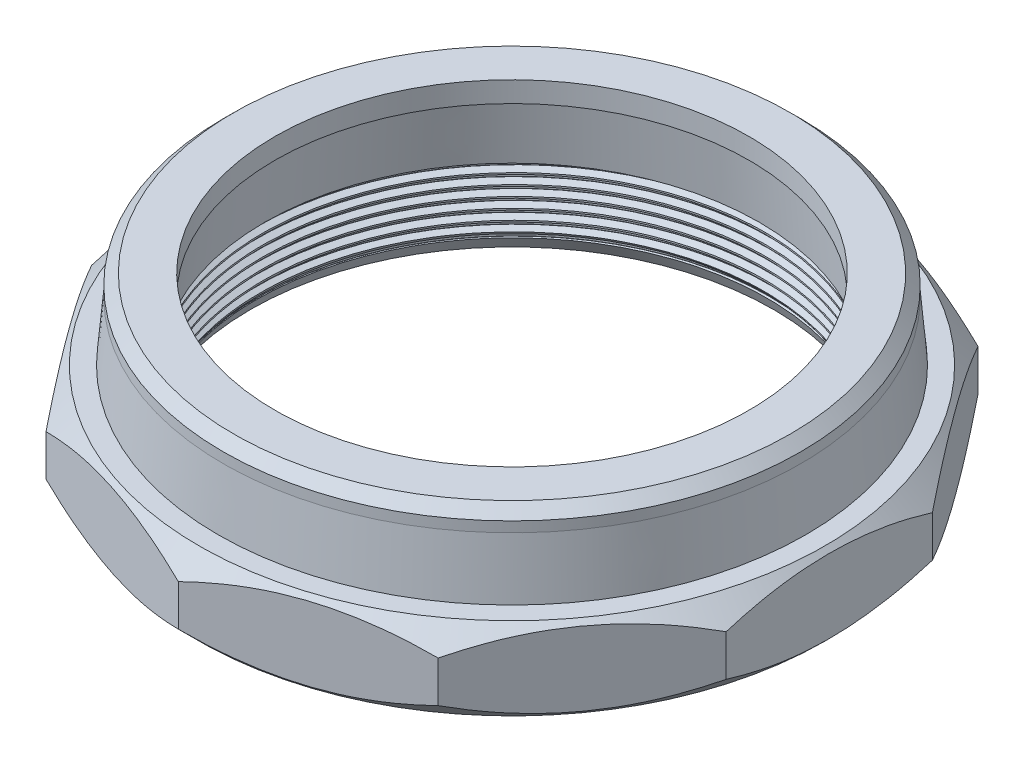
SolidWorks part; units mm, degrees
material "ABS"
ref_plane "Спереди" through (0, 0, 0) normal (0, 0, 1) x (1, 0, 0)
ref_plane "Сверху" through (0, 0, 0) normal (0, 1, 0) x (1, 0, 0)
ref_plane "Справа" through (0, 0, 0) normal (1, 0, 0) x (0, 0, -1)
sketch "Эскиз1" plane through (0, 0, 0) normal (0, 0, 1) x (1, 0, 0)
  line L0 (0, 9.0507) -> (0, -9.1503) construction
  line L1 (24.36, -8) -> (24.36, 0)
  line L3 (24.36, -8) -> (29.3544, -8)
  line L5 (28.5, 0) -> (28, 5.715)
  line L7 (23.5, 5.715) -> (23, 5.715)
  line L8 (23, 5.715) -> (23, 7.715)
  line L9 (23, 7.715) -> (28, 7.715)
  line L10 (28, 7.715) -> (28, 5.715)
  line L11 (28.5, 0) -> (30.36, 0)
  line L12 (32.36, -2) -> (32.36, -6)
  line L13 (30.36, -8) -> (29.3544, -8)
  line L14 (30.36, 0) -> (32.36, -2)
  line L15 (32.36, -6) -> (30.36, -8)
  line L18 (24, 0) -> (23.5, 5.715)
  line L19 (24, 0) -> (24.36, 0)
  dimension "D2" = 2
  dimension "D3" = 24.36
  dimension "D4" = 2
  dimension "D5" = 45
  dimension "D6" = 45
  dimension "D7" = 24
  dimension "D8" = 5
  dimension "D9" = 23
  dimension "D10" = 6
  dimension "D11" = 2
  dimension "D12" = 5
  dimension "D13" = 8
  dimension "D14" = 8
  dimension "D15" = 0.5
revolve "Повернуть1" add sketch "Эскиз1" angle 360 about L0
sketch "Эскиз2" plane through (0, 0, 0) normal (0, 1, 0) x (1, 0, 0)
  line L0 (0, 32.36) -> (0, -32.36) construction
  line L10 (0, 32.36) -> (-19.0207, 26.1798)
  line L11 (-19.0207, 26.1798) -> (-30.7762, 9.9998)
  line L12 (-30.7762, 9.9998) -> (-30.7762, -9.9998)
  line L13 (-30.7762, -9.9998) -> (-19.0207, -26.1798)
  line L14 (-19.0207, -26.1798) -> (0, -32.36)
  line L15 (0, -32.36) -> (19.0207, -26.1798)
  line L16 (19.0207, -26.1798) -> (30.7762, -9.9998)
  line L17 (30.7762, -9.9998) -> (30.7762, 9.9998)
  line L18 (30.7762, 9.9998) -> (19.0207, 26.1798)
  line L19 (19.0207, 26.1798) -> (0, 32.36)
  circle A0 centre (0, 0) radius 32.36 construction
  circle A1 centre (0, 0) radius 30.7762 construction
extrude "Вырез-Вытянуть3" cut sketch "Эскиз2" against normal blind 10 flip side to cut
chamfer "Фаска1" distance 2 distance2 1 1 edges at (-24.36, -8, 0) first distance on face at (-24.36, -8, 0)
chamfer "Фаска2" distance 1 angle 45 1 edges at (-28, 7.715, 0)
sketch "Эскиз3" plane through (0, 0, 0) normal (0, -1, 0) x (1, 0, 0)
  circle A0 centre (0, 0) radius 24.36
  dimension "D1" = 48.72
curve "Спираль1" pitch 1 height 19.5 radius 24.36 left hand yes centre (0, 0, 0) axis (0, -1, 0) start towards (0, 0, 1)
ref_plane "Плоскость2" through (0, 0, 0) normal (-1, 0, 0) x (0, 0, 1)
sketch "Эскиз4" plane through (0, 0, 0) normal (-1, 0, 0) x (0, 0, 1)
  line L4 (-24.36, -19.925) -> (-24.36, -19.075) construction
  line L5 (-24.36, -19.075) -> (-24.8796, -19.375)
  line L6 (-24.8796, -19.375) -> (-24.8796, -19.625) construction
  line L7 (-24.8796, -19.625) -> (-24.36, -19.925)
  line L8 (-24.36, -19.5) -> (-24.8796, -19.5) construction
  line L9 (-24.8796, -19.375) -> (-24.9096, -19.375)
  line L10 (-24.9096, -19.375) -> (-24.9096, -19.625)
  line L11 (-24.9096, -19.625) -> (-24.8796, -19.625)
  line L12 (-24.36, -19.075) -> (-24.26, -19.0173)
  line L13 (-24.26, -19.0173) -> (-24.26, -19.9827)
  line L14 (-24.26, -19.9827) -> (-24.36, -19.925)
  line L15 (0, 0) -> (0, -30) construction
  spline S1 degree 3 poles (24.36, 0) (24.36, -0.0152) (23.6837, -0.0458) (20.7235, -0.0915) (16.0609, -0.1373) (10.0789, -0.1831) (3.2689, -0.2289) (-3.8097, -0.2746) (-10.5753, -0.3204) (-16.4721, -0.3662) (-21.0157, -0.412) (-23.8329, -0.4577) (-24.6921, -0.5035) (-23.5229, -0.5493) (-20.4212, -0.5951) (-15.6419, -0.6408) (-9.5776, -0.6866) (-2.7265, -0.7324) (4.3486, -0.7782) (11.0664, -0.8239) (16.8752, -0.8697) (21.2976, -0.9155) (23.9704, -0.9613) (24.674, -1.007) (23.3506, -1.0528) (20.1089, -1.0986) (15.2153, -1.1444) (9.0717, -1.1901) (2.1828, -1.2359) (-4.8853, -1.2817) (-11.5522, -1.3275) (-17.27, -1.3732) (-21.569, -1.419) (-24.0962, -1.4648) (-24.6438, -1.5106) (-23.1669, -1.5563) (-19.7868, -1.6021) (-14.7812, -1.6479) (-8.5613, -1.6937) (-1.6381, -1.7394) (5.4197, -1.7852) (12.0323, -1.831) (17.6564, -1.8768) (21.8299, -1.9225) (24.2102, -1.9683) (24.6015, -2.0141) (22.9718, -2.0599) (19.4549, -2.1056) (14.3398, -2.1514) (8.0467, -2.1972) (1.0925, -2.243) (-5.9515, -2.2887) (-12.5065, -2.3345) (-18.0341, -2.3803) (-22.0802, -2.4261) (-24.3123, -2.4718) (-24.5472, -2.5176) (-22.7655, -2.5634) (-19.1136, -2.6092) (-13.8915, -2.6549) (-7.5281, -2.7007) (-0.5464, -2.7465) (6.4803, -2.7923) (12.9746, -2.838) (18.403, -2.8838) (22.3196, -2.9296) (24.4026, -2.9754) (24.4809, -3.0211) (22.5481, -3.0669) (18.7629, -3.1127) (13.4363, -3.1585) (7.0059, -3.2042) (0, -3.25) (-7.0059, -3.2958) (-13.4363, -3.3415) (-18.7629, -3.3873) (-22.5481, -3.4331) (-24.4809, -3.4789) (-24.4026, -3.5246) (-22.3196, -3.5704) (-18.403, -3.6162) (-12.9746, -3.662) (-6.4803, -3.7077) (0.5464, -3.7535) (7.5281, -3.7993) (13.8915, -3.8451) (19.1136, -3.8908) (22.7655, -3.9366) (24.5472, -3.9824) (24.3123, -4.0282) (22.0802, -4.0739) (18.0341, -4.1197) (12.5065, -4.1655) (5.9515, -4.2113) (-1.0925, -4.257) (-8.0467, -4.3028) (-14.3398, -4.3486) (-19.4549, -4.3944) (-22.9718, -4.4401) (-24.6015, -4.4859) (-24.2102, -4.5317) (-21.8299, -4.5775) (-17.6564, -4.6232) (-12.0323, -4.669) (-5.4197, -4.7148) (1.6381, -4.7606) (8.5613, -4.8063) (14.7812, -4.8521) (19.7868, -4.8979) (23.1669, -4.9437) (24.6438, -4.9894) (24.0962, -5.0352) (21.569, -5.081) (17.27, -5.1268) (11.5522, -5.1725) (4.8853, -5.2183) (-2.1828, -5.2641) (-9.0717, -5.3099) (-15.2153, -5.3556) (-20.1089, -5.4014) (-23.3506, -5.4472) (-24.674, -5.493) (-23.9704, -5.5387) (-21.2976, -5.5845) (-16.8752, -5.6303) (-11.0664, -5.6761) (-4.3486, -5.7218) (2.7265, -5.7676) (9.5776, -5.8134) (15.6419, -5.8592) (20.4212, -5.9049) (23.5229, -5.9507) (24.6921, -5.9965) (23.8329, -6.0423) (21.0157, -6.088) (16.4721, -6.1338) (10.5753, -6.1796) (3.8097, -6.2254) (-3.2689, -6.2711) (-10.0789, -6.3169) (-16.0609, -6.3627) (-20.7235, -6.4085) (-23.6837, -6.4542) (-24.6982, -6.5) (-23.6837, -6.5458) (-20.7235, -6.5915) (-16.0609, -6.6373) (-10.0789, -6.6831) (-3.2689, -6.7289) (3.8097, -6.7746) (10.5753, -6.8204) (16.4721, -6.8662) (21.0157, -6.912) (23.8329, -6.9577) (24.6921, -7.0035) (23.5229, -7.0493) (20.4212, -7.0951) (15.6419, -7.1408) (9.5776, -7.1866) (2.7265, -7.2324) (-4.3486, -7.2782) (-11.0664, -7.3239) (-16.8752, -7.3697) (-21.2976, -7.4155) (-23.9704, -7.4613) (-24.674, -7.507) (-23.3506, -7.5528) (-20.1089, -7.5986) (-15.2153, -7.6444) (-9.0717, -7.6901) (-2.1828, -7.7359) (4.8853, -7.7817) (11.5522, -7.8275) (17.27, -7.8732) (21.569, -7.919) (24.0962, -7.9648) (24.6438, -8.0106) (23.1669, -8.0563) (19.7868, -8.1021) (14.7812, -8.1479) (8.5613, -8.1937) (1.6381, -8.2394) (-5.4197, -8.2852) (-12.0323, -8.331) (-17.6564, -8.3768) (-21.8299, -8.4225) (-24.2102, -8.4683) (-24.6015, -8.5141) (-22.9718, -8.5599) (-19.4549, -8.6056) (-14.3398, -8.6514) (-8.0467, -8.6972) (-1.0925, -8.743) (5.9515, -8.7887) (12.5065, -8.8345) (18.0341, -8.8803) (22.0802, -8.9261) (24.3123, -8.9718) (24.5472, -9.0176) (22.7655, -9.0634) (19.1136, -9.1092) (13.8915, -9.1549) (7.5281, -9.2007) (0.5464, -9.2465) (-6.4803, -9.2923) (-12.9746, -9.338) (-18.403, -9.3838) (-22.3196, -9.4296) (-24.4026, -9.4754) (-24.4809, -9.5211) (-22.5481, -9.5669) (-18.7629, -9.6127) (-13.4363, -9.6585) (-7.0059, -9.7042) (0, -9.75) (7.0059, -9.7958) (13.4363, -9.8415) (18.7629, -9.8873) (22.5481, -9.9331) (24.4809, -9.9789) (24.4026, -10.0246) (22.3196, -10.0704) (18.403, -10.1162) (12.9746, -10.162) (6.4803, -10.2077) (-0.5464, -10.2535) (-7.5281, -10.2993) (-13.8915, -10.3451) (-19.1136, -10.3908) (-22.7655, -10.4366) (-24.5472, -10.4824) (-24.3123, -10.5282) (-22.0802, -10.5739) (-18.0341, -10.6197) (-12.5065, -10.6655) (-5.9515, -10.7113) (1.0925, -10.757) (8.0467, -10.8028) (14.3398, -10.8486) (19.4549, -10.8944) (22.9718, -10.9401) (24.6015, -10.9859) (24.2102, -11.0317) (21.8299, -11.0775) (17.6564, -11.1232) (12.0323, -11.169) (5.4197, -11.2148) (-1.6381, -11.2606) (-8.5613, -11.3063) (-14.7812, -11.3521) (-19.7868, -11.3979) (-23.1669, -11.4437) (-24.6438, -11.4894) (-24.0962, -11.5352) (-21.569, -11.581) (-17.27, -11.6268) (-11.5522, -11.6725) (-4.8853, -11.7183) (2.1828, -11.7641) (9.0717, -11.8099) (15.2153, -11.8556) (20.1089, -11.9014) (23.3506, -11.9472) (24.674, -11.993) (23.9704, -12.0387) (21.2976, -12.0845) (16.8752, -12.1303) (11.0664, -12.1761) (4.3486, -12.2218) (-2.7265, -12.2676) (-9.5776, -12.3134) (-15.6419, -12.3592) (-20.4212, -12.4049) (-23.5229, -12.4507) (-24.6921, -12.4965) (-23.8329, -12.5423) (-21.0157, -12.588) (-16.4721, -12.6338) (-10.5753, -12.6796) (-3.8097, -12.7254) (3.2689, -12.7711) (10.0789, -12.8169) (16.0609, -12.8627) (20.7235, -12.9085) (23.6837, -12.9542) (24.6982, -13) (23.6837, -13.0458) (20.7235, -13.0915) (16.0609, -13.1373) (10.0789, -13.1831) (3.2689, -13.2289) (-3.8097, -13.2746) (-10.5753, -13.3204) (-16.4721, -13.3662) (-21.0157, -13.412) (-23.8329, -13.4577) (-24.6921, -13.5035) (-23.5229, -13.5493) (-20.4212, -13.5951) (-15.6419, -13.6408) (-9.5776, -13.6866) (-2.7265, -13.7324) (4.3486, -13.7782) (11.0664, -13.8239) (16.8752, -13.8697) (21.2976, -13.9155) (23.9704, -13.9613) (24.674, -14.007) (23.3506, -14.0528) (20.1089, -14.0986) (15.2153, -14.1444) (9.0717, -14.1901) (2.1828, -14.2359) (-4.8853, -14.2817) (-11.5522, -14.3275) (-17.27, -14.3732) (-21.569, -14.419) (-24.0962, -14.4648) (-24.6438, -14.5106) (-23.1669, -14.5563) (-19.7868, -14.6021) (-14.7812, -14.6479) (-8.5613, -14.6937) (-1.6381, -14.7394) (5.4197, -14.7852) (12.0323, -14.831) (17.6564, -14.8768) (21.8299, -14.9225) (24.2102, -14.9683) (24.6015, -15.0141) (22.9718, -15.0599) (19.4549, -15.1056) (14.3398, -15.1514) (8.0467, -15.1972) (1.0925, -15.243) (-5.9515, -15.2887) (-12.5065, -15.3345) (-18.0341, -15.3803) (-22.0802, -15.4261) (-24.3123, -15.4718) (-24.5472, -15.5176) (-22.7655, -15.5634) (-19.1136, -15.6092) (-13.8915, -15.6549) (-7.5281, -15.7007) (-0.5464, -15.7465) (6.4803, -15.7923) (12.9746, -15.838) (18.403, -15.8838) (22.3196, -15.9296) (24.4026, -15.9754) (24.4809, -16.0211) (22.5481, -16.0669) (18.7629, -16.1127) (13.4363, -16.1585) (7.0059, -16.2042) (0, -16.25) (-7.0059, -16.2958) (-13.4363, -16.3415) (-18.7629, -16.3873) (-22.5481, -16.4331) (-24.4809, -16.4789) (-24.4026, -16.5246) (-22.3196, -16.5704) (-18.403, -16.6162) (-12.9746, -16.662) (-6.4803, -16.7077) (0.5464, -16.7535) (7.5281, -16.7993) (13.8915, -16.8451) (19.1136, -16.8908) (22.7655, -16.9366) (24.5472, -16.9824) (24.3123, -17.0282) (22.0802, -17.0739) (18.0341, -17.1197) (12.5065, -17.1655) (5.9515, -17.2113) (-1.0925, -17.257) (-8.0467, -17.3028) (-14.3398, -17.3486) (-19.4549, -17.3944) (-22.9718, -17.4401) (-24.6015, -17.4859) (-24.2102, -17.5317) (-21.8299, -17.5775) (-17.6564, -17.6232) (-12.0323, -17.669) (-5.4197, -17.7148) (1.6381, -17.7606) (8.5613, -17.8063) (14.7812, -17.8521) (19.7868, -17.8979) (23.1669, -17.9437) (24.6438, -17.9894) (24.0962, -18.0352) (21.569, -18.081) (17.27, -18.1268) (11.5522, -18.1725) (4.8853, -18.2183) (-2.1828, -18.2641) (-9.0717, -18.3099) (-15.2153, -18.3556) (-20.1089, -18.4014) (-23.3506, -18.4472) (-24.674, -18.493) (-23.9704, -18.5387) (-21.2976, -18.5845) (-16.8752, -18.6303) (-11.0664, -18.6761) (-4.3486, -18.7218) (2.7265, -18.7676) (9.5776, -18.8134) (15.6419, -18.8592) (20.4212, -18.9049) (23.5229, -18.9507) (24.6921, -18.9965) (23.8329, -19.0423) (21.0157, -19.088) (16.4721, -19.1338) (10.5753, -19.1796) (3.8097, -19.2254) (-3.2689, -19.2711) (-10.0789, -19.3169) (-16.0609, -19.3627) (-20.7235, -19.4085) (-23.6837, -19.4542) (-24.36, -19.4848) (-24.36, -19.5) knots 0 0 0 0 0.002347 0.004695 0.007042 0.00939 0.011737 0.014085 0.016432 0.018779 0.021127 0.023474 0.025822 0.028169 0.030516 0.032864 0.035211 0.037559 0.039906 0.042254 0.044601 0.046948 0.049296 0.051643 0.053991 0.056338 0.058685 0.061033 0.06338 0.065728 0.068075 0.070423 0.07277 0.075117 0.077465 0.079812 0.08216 0.084507 0.086854 0.089202 0.091549 0.093897 0.096244 0.098592 0.100939 0.103286 0.105634 0.107981 0.110329 0.112676 0.115023 0.117371 0.119718 0.122066 0.124413 0.126761 0.129108 0.131455 0.133803 0.13615 0.138498 0.140845 0.143192 0.14554 0.147887 0.150235 0.152582 0.15493 0.157277 0.159624 0.161972 0.164319 0.166667 0.169014 0.171362 0.173709 0.176056 0.178404 0.180751 0.183099 0.185446 0.187793 0.190141 0.192488 0.194836 0.197183 0.199531 0.201878 0.204225 0.206573 0.20892 0.211268 0.213615 0.215962 0.21831 0.220657 0.223005 0.225352 0.2277 0.230047 0.232394 0.234742 0.237089 0.239437 0.241784 0.244131 0.246479 0.248826 0.251174 0.253521 0.255869 0.258216 0.260563 0.262911 0.265258 0.267606 0.269953 0.2723 0.274648 0.276995 0.279343 0.28169 0.284038 0.286385 0.288732 0.29108 0.293427 0.295775 0.298122 0.300469 0.302817 0.305164 0.307512 0.309859 0.312207 0.314554 0.316901 0.319249 0.321596 0.323944 0.326291 0.328638 0.330986 0.333333 0.335681 0.338028 0.340376 0.342723 0.34507 0.347418 0.349765 0.352113 0.35446 0.356808 0.359155 0.361502 0.36385 0.366197 0.368545 0.370892 0.373239 0.375587 0.377934 0.380282 0.382629 0.384977 0.387324 0.389671 0.392019 0.394366 0.396714 0.399061 0.401408 0.403756 0.406103 0.408451 0.410798 0.413146 0.415493 0.41784 0.420188 0.422535 0.424883 0.42723 0.429577 0.431925 0.434272 0.43662 0.438967 0.441315 0.443662 0.446009 0.448357 0.450704 0.453052 0.455399 0.457746 0.460094 0.462441 0.464789 0.467136 0.469484 0.471831 0.474178 0.476526 0.478873 0.481221 0.483568 0.485915 0.488263 0.49061 0.492958 0.495305 0.497653 0.5 0.502347 0.504695 0.507042 0.50939 0.511737 0.514085 0.516432 0.518779 0.521127 0.523474 0.525822 0.528169 0.530516 0.532864 0.535211 0.537559 0.539906 0.542254 0.544601 0.546948 0.549296 0.551643 0.553991 0.556338 0.558685 0.561033 0.56338 0.565728 0.568075 0.570423 0.57277 0.575117 0.577465 0.579812 0.58216 0.584507 0.586854 0.589202 0.591549 0.593897 0.596244 0.598592 0.600939 0.603286 0.605634 0.607981 0.610329 0.612676 0.615023 0.617371 0.619718 0.622066 0.624413 0.626761 0.629108 0.631455 0.633803 0.63615 0.638498 0.640845 0.643192 0.64554 0.647887 0.650235 0.652582 0.65493 0.657277 0.659624 0.661972 0.664319 0.666667 0.669014 0.671362 0.673709 0.676056 0.678404 0.680751 0.683099 0.685446 0.687793 0.690141 0.692488 0.694836 0.697183 0.699531 0.701878 0.704225 0.706573 0.70892 0.711268 0.713615 0.715962 0.71831 0.720657 0.723005 0.725352 0.7277 0.730047 0.732394 0.734742 0.737089 0.739437 0.741784 0.744131 0.746479 0.748826 0.751174 0.753521 0.755869 0.758216 0.760563 0.762911 0.765258 0.767606 0.769953 0.7723 0.774648 0.776995 0.779343 0.78169 0.784038 0.786385 0.788732 0.79108 0.793427 0.795775 0.798122 0.800469 0.802817 0.805164 0.807512 0.809859 0.812207 0.814554 0.816901 0.819249 0.821596 0.823944 0.826291 0.828638 0.830986 0.833333 0.835681 0.838028 0.840376 0.842723 0.84507 0.847418 0.849765 0.852113 0.85446 0.856808 0.859155 0.861502 0.86385 0.866197 0.868545 0.870892 0.873239 0.875587 0.877934 0.880282 0.882629 0.884977 0.887324 0.889671 0.892019 0.894366 0.896714 0.899061 0.901408 0.903756 0.906103 0.908451 0.910798 0.913146 0.915493 0.91784 0.920188 0.922535 0.924883 0.92723 0.929577 0.931925 0.934272 0.93662 0.938967 0.941315 0.943662 0.946009 0.948357 0.950704 0.953052 0.955399 0.957746 0.960094 0.962441 0.964789 0.967136 0.969484 0.971831 0.974178 0.976526 0.978873 0.981221 0.983568 0.985915 0.988263 0.99061 0.992958 0.995305 0.997653 1 1 1 1 construction
  dimension "D1" = 0.85
  dimension "D2" = 0.25
  dimension "D3" = 60
  dimension "D4" = 0.03
  dimension "D5" = 0.1
sweep "Вырез-По траектории1" cut profiles "Эскиз4" path "Спираль1" align with end faces yes
